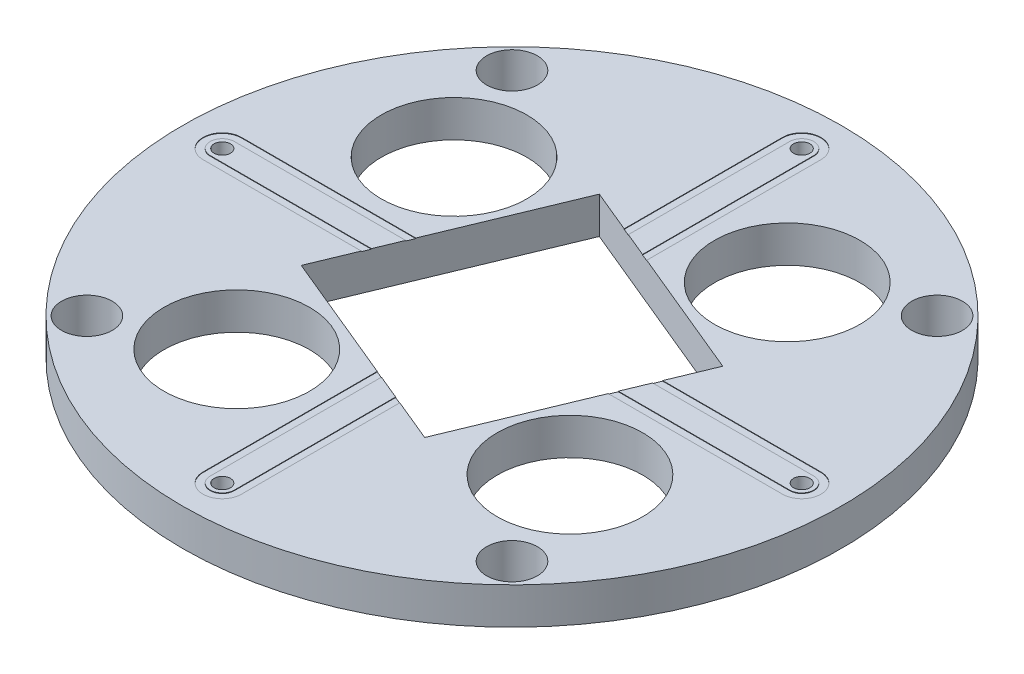
SolidWorks part; units mm, degrees
material "Ceramic Porcelain"
ref_plane "Front Plane" through (0, 0, 0) normal (0, 0, 1) x (1, 0, 0)
ref_plane "Top Plane" through (0, 0, 0) normal (0, 1, 0) x (1, 0, 0)
ref_plane "Right Plane" through (0, 0, 0) normal (1, 0, 0) x (0, 0, -1)
ref_axis "Y Axis" through (0, 0.0762, 0) along (0, -1, 0)
sketch "Boday Sketch" plane through (0, 0, 0) normal (0, 1, 0) x (1, 0, 0)
  circle A0 centre (0, 0) radius 11.557
  dimension "D1" = 23.114
extrude "Body" add sketch "Boday Sketch" against normal blind 1.27
sketch "Copper Sketch" plane through (0, 0, 0) normal (0, 1, 0) x (1, 0, 0)
  circle A0 centre (0, 0) radius 11.557
  dimension "D1" = 23.114
extrude "Copper" add sketch "Copper Sketch" along normal blind 0.0175
sketch "Screw Position" plane through (0, 0, 0) normal (0, 1, 0) x (1, 0, 0)
  point P0 (-7.4536, 7.4536)
sketch "IO Hole Positions" plane through (0, 0, 0) normal (0, 1, 0) x (1, 0, 0)
  point P0 (-3.8881, 9.3866)
  point P1 (3.8881, 9.3866)
  point P5 (9.3866, 3.8881)
  point P6 (9.3866, -3.8881)
  point P7 (3.8881, -9.3866)
  point P8 (-3.8881, -9.3866)
  point P9 (-9.3866, -3.8881)
  point P10 (-9.3866, 3.8881)
  point P11 (0, 0)
  dimension "D2" = 8
sketch "Gap" plane through (0, 0, 0) normal (0, 1, 0) x (1, 0, 0)
  line L2 (0.675, 0) -> (0.675, 10.16)
  line L4 (-0.675, 10.16) -> (-0.675, 0)
  line L5 (-0.675, 0) -> (0.675, 0)
  arc A2 (0.675, 10.16) -> (-0.675, 10.16) centre (0, 10.16) ccw
  point P0 (0.675, 0)
  dimension "D2" = 10.16
sketch "Center Sketch" plane through (0, 0, 0) normal (0, 1, 0) x (1, 0, 0)
  line L0 (0.425, 0) -> (0.425, 10.16)
  line L3 (-0.425, 10.16) -> (-0.425, 0)
  line L4 (-0.425, 0) -> (0.425, 0)
  arc A1 (0.425, 10.16) -> (-0.425, 10.16) centre (0, 10.16) ccw
  point P0 (0.425, 0)
  point P3 (0.425, 10.16)
  dimension "D2" = 10.16
hole_wizard "#0 Clearance Hole1" positions "Sketch23" profile "Sketch24" hole size "#0" standard "ANSI Inch" end condition through all
sketch "Sketch23" plane through (0, 0.0175, 0) normal (0, 1, 0) x (-1, 0, 0)
  point P2 (7.4536, -7.4536)
sketch "Sketch24" plane through (-7.4536, 0.0175, -7.4536) normal (1, 0, 0) x (0, 0, 1)
  line L0 (0, 0) -> (0, 1.2875)
  line L1 (0, 1.2875) -> (0.889, 1.2875)
  line L2 (0.889, 1.2875) -> (0.889, 0)
  line L5 (0.889, 0) -> (0, 0)
  line L11 (0, -6.35) -> (0, 107.95) construction
  dimension "Thru Hole Dia." = 1.778
  dimension "Thru Hole Depth" = 1.2875
pattern_circular "Screw Holes" count 4 over 360 about axis through (0, 0.0762, 0) along (0, -1, 0) of "#0 Clearance Hole1"
extrude "Gap Cut" cut sketch "Gap" along normal through all
extrude "Center" add sketch "Center Sketch" along normal blind 0.0175 separate body
sketch "IO Hole Sketch" plane through (0, 0, 0) normal (0, 1, 0) x (1, 0, 0)
  circle A0 centre (0, 10.16) radius 0.287
  dimension "D1" = 0.574
extrude "IO Hole" cut sketch "IO Hole Sketch" against normal through all and the other way through all
pattern_circular "Gap Cuts" count 4 over 360 about axis through (0, 0.0762, 0) along (0, -1, 0) of "Gap Cut"
pattern_circular "Centers" count 4 over 360 about axis through (0, 0.0762, 0) along (0, -1, 0) of "Center"
pattern_circular "IO Holes" count 4 over 360 about axis through (0, 0.0762, 0) along (0, -1, 0) of "IO Hole"
sketch "Pocket Sketch" plane through (0, 0, 0) normal (0, 1, 0) x (1, 0, 0)
  line L1 (-5.2263, -2.1648) -> (2.1648, -5.2263)
  line L2 (-5.2263, -2.1648) -> (-2.1648, 5.2263)
  line L3 (-2.1648, 5.2263) -> (5.2263, 2.1648)
  line L4 (2.1648, -5.2263) -> (5.2263, 2.1648)
  line L5 (-5.2263, -2.1648) -> (5.2263, 2.1648) construction
  line L6 (-2.1648, 5.2263) -> (2.1648, -5.2263) construction
  point P0 (0, 0)
  dimension "D2" = 8
  dimension "D1" = 8
extrude "Pocket" cut sketch "Pocket Sketch" against normal through all and the other way through all
sketch "Posts" plane through (0, 0, 0) normal (0, 1, 0) x (1, 0, 0)
  circle A9 centre (3.81, 5.842) radius 2.5527
  dimension "D3" = 5.1054
  dimension "D1" = 3.81
  dimension "D2" = 5.842
extrude "Post Cut" cut sketch "Posts" against normal through all and the other way through all
pattern_circular "Post Cuts" count 4 over 360 about axis through (0, 0.0762, 0) along (0, -1, 0) of "Post Cut"
equation "\"mount_d\"= 0.91in"
equation "\"dieletric_h\"= 0.05in"
equation "\"D1@Boday Sketch\" = \"mount_d\""
equation "\"D1@Body\" = \"dieletric_h\""
equation "\"screw_inner_r\"= 0.415in"
equation "\"io_r\"= 0.4in"
equation "\"D1@Screw Position\" = \"screw_inner_r\""
equation "\"D1@IO Hole Positions\" = \"io_r\""
equation "\"io_hole_d\"= 0.574mm"
equation "\"D1@IO Hole Sketch\" = \"io_hole_d\""
equation "\"W\"= 0.85mm"
equation "\"G\"= 0.25mm"
equation "\"copper_t\"= 17.5um"
equation "\"silicon_size\"= 8mm"
equation "\"D1@Center\" = \"copper_t\""
equation "\"D1@Copper\"=\"copper_t\""
equation "\"D1@Pocket Sketch\" = \"silicon_size\""
equation "\"D2@Pocket Sketch\" = \"silicon_size\""
equation "\"post_x\"= 0.15in"
equation "\"post_z\"= 0.23in"
equation "\"post_d\"= 0.201in"
equation "\"D1@Posts\"=\"post_x\""
equation "\"D2@Posts\"=\"post_z\""
equation "\"D3@Posts\"=\"post_d\""
equation "\"D1@Gap\"=\"W\" / 2 + \"G\""
equation "\"D2@Gap\"=\"io_r\""
equation "\"D1@Center Sketch\"=\"W\" / 2"
equation "\"D2@Center Sketch\"=\"io_r\""
